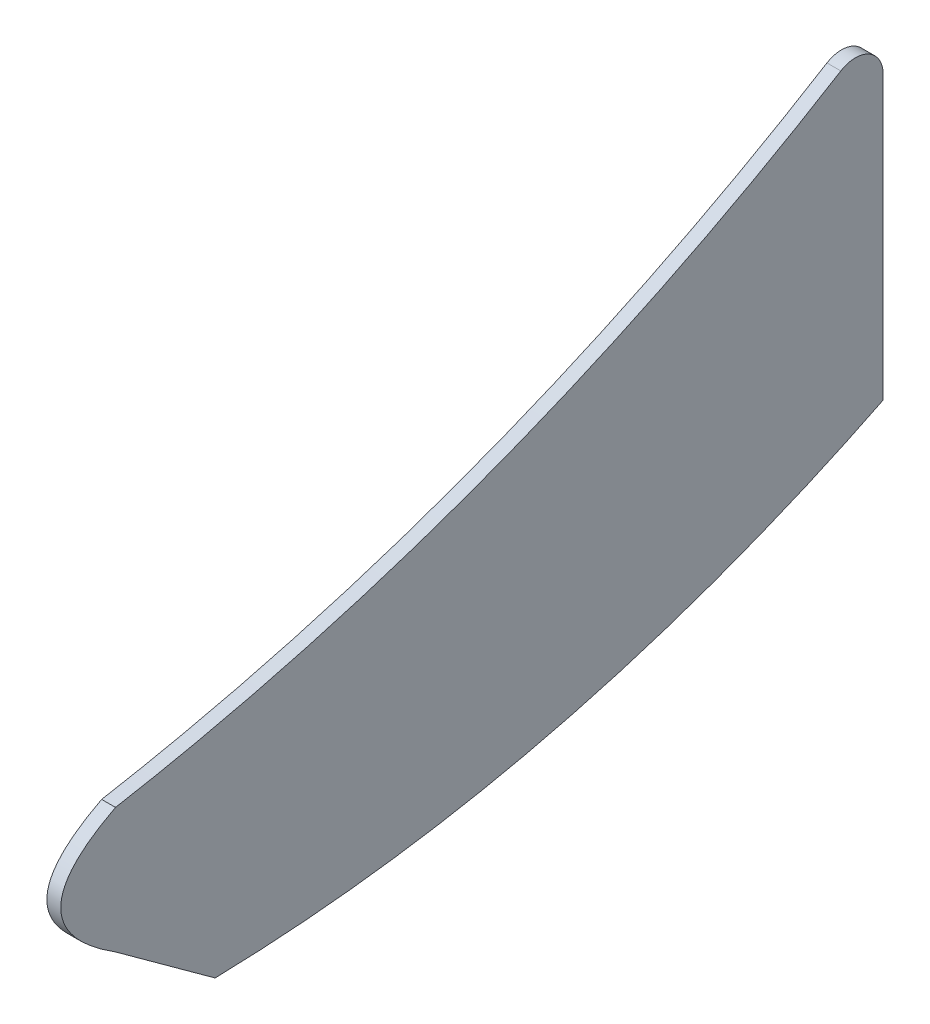
SolidWorks part; units mm, degrees
ref_plane "Front Plane" through (0, 0, 0) normal (0, 0, 1) x (1, 0, 0)
ref_plane "Top Plane" through (0, 0, 0) normal (0, 1, 0) x (1, 0, 0)
ref_plane "Right Plane" through (0, 0, 0) normal (1, 0, 0) x (0, 0, -1)
sketch "Sketch1" plane through (0, 0, 0) normal (1, 0, 0) x (0, 0, -1)
  line L3 (552.2102, -51.4345) -> (552.2102, 253.3655)
  line L4 (-59.3103, -203.8345) -> (-150.5079, -137.593)
  spline S0 degree 2 poles (-59.3103, -203.8345) (261.653, -195.8813) (552.2102, -51.4345) knots 0 0 0 1 1 1
  spline S1 degree 2 poles (552.2102, 253.3655) (229.842, 44.5732) (-150.5079, -22.9788) knots 0 0 0 1 1 1
  spline S2 degree 2 poles (-150.5079, -22.9788) (-250.7603, -74.4603) (-150.5079, -137.593) knots 0 0 0 1 1 1
  dimension "D1" = 304.8
extrude "Boss-Extrude1" add sketch "Sketch1" along normal blind 12.7 contours S0 L3 S1 S2 L4
fillet "Fillet1" radius 25.4 1 edges at (6.35, 253.3655, -552.2102)
fillet "Fillet2" radius 25.4 1 edges at (6.35, -137.593, 150.5079)
